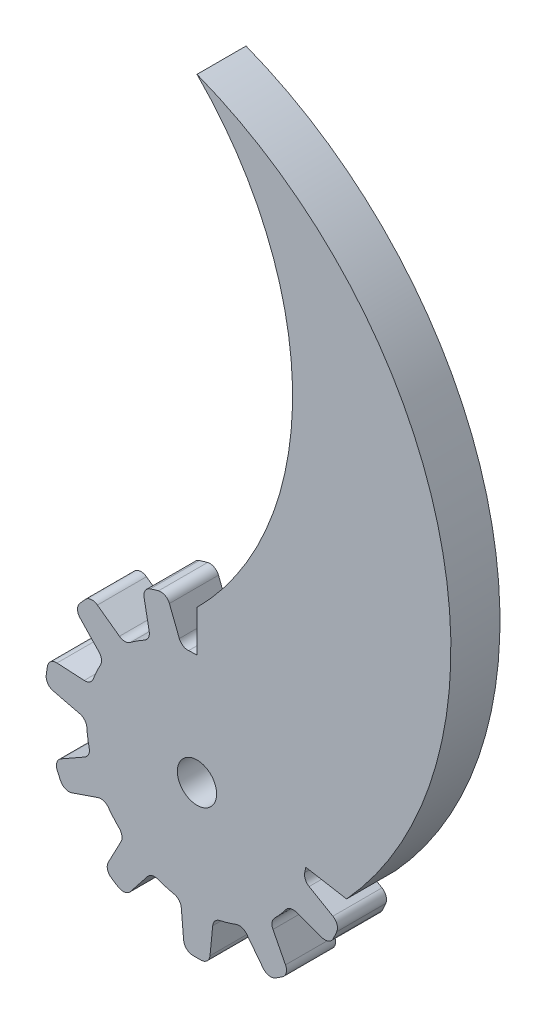
SolidWorks part; units mm, degrees
material "ABS"
ref_plane "Plano frontal" through (0, 0, 0) normal (0, 0, 1) x (1, 0, 0)
ref_plane "Plano superior" through (0, 0, 0) normal (0, 1, 0) x (1, 0, 0)
ref_plane "Plano direito" through (0, 0, 0) normal (1, 0, 0) x (0, 0, -1)
sketch "Esboço1" plane through (0, 0, 0) normal (0, 0, 1) x (1, 0, 0)
  line L0 (-5.4289, -10.4113) -> (-4.0402, -8.6536)
  line L1 (-7.2321, -9.242) -> (-6.1976, -7.2764)
  line L2 (-10.1959, -5.8234) -> (-8.0773, -5.0956)
  line L3 (-11.0806, -3.8649) -> (-9.1477, -2.7707)
  line L4 (-11.7257, 0.6133) -> (-9.5499, 0.0802)
  line L5 (-11.4112, 2.7393) -> (-9.1935, 2.6148)
  line L6 (-9.5327, 6.8553) -> (-7.9905, 5.2306)
  line L7 (-8.1187, 8.4738) -> (-6.3204, 7.1701)
  line L8 (-4.3131, 10.9208) -> (-3.8942, 8.7202)
  line L9 (-2.2487, 11.5179) -> (-1.4406, 9.4489)
  line L10 (1.0616, -11.6936) -> (1.2797, -9.4641)
  line L11 (-1.0874, -11.6849) -> (-1.2798, -9.472)
  line L12 (2.2758, 11.519) -> (1.4385, 9.4413)
  line L13 (4.3354, 10.9052) -> (3.8965, 8.7278)
  line L14 (8.1422, 8.46) -> (6.3145, 7.1648)
  line L15 (9.5429, 6.8302) -> (7.9966, 5.2356)
  line L16 (11.4235, 2.715) -> (9.1857, 2.6136)
  line L17 (11.7207, 0.5866) -> (9.5577, 0.0812)
  line L18 (11.0779, -3.892) -> (9.1405, -2.7675)
  line L19 (10.1772, -5.8432) -> (8.0844, -5.099)
  line L20 (7.2152, -9.2633) -> (6.1933, -7.2699)
  line L21 (5.4025, -10.4178) -> (4.0443, -8.6603)
  arc A0 (1.8703, -8.8035) -> (3.1854, -8.4174) centre (0, 0) ccw
  circle A1 centre (0, 0) radius 1.6
  arc A2 (-0.3622, -12.3696) -> (0.3355, -12.3703) centre (0, 0) ccw
  arc A3 (-1.0874, -11.6849) -> (-0.3622, -12.3696) centre (-0.3402, -11.6199) ccw
  arc A4 (1.0616, -11.6936) -> (0.3355, -12.3703) centre (0.3152, -11.6206) cw
  arc A5 (-6.9922, -10.2102) -> (-6.4056, -10.588) centre (0, 0) ccw
  arc A6 (-7.2321, -9.242) -> (-6.9922, -10.2102) centre (-6.5684, -9.5913) ccw
  arc A7 (-5.4289, -10.4113) -> (-6.4056, -10.588) centre (-6.0174, -9.9463) cw
  arc A8 (-11.4022, -4.8091) -> (-11.1131, -5.444) centre (0, 0) ccw
  arc A9 (-11.0806, -3.8649) -> (-11.4022, -4.8091) centre (-10.7112, -4.5176) ccw
  arc A10 (-10.1959, -5.8234) -> (-11.1131, -5.444) centre (-10.4395, -5.1141) cw
  arc A11 (-12.1921, 2.1188) -> (-12.2922, 1.4284) centre (0, 0) ccw
  arc A12 (-11.4112, 2.7393) -> (-12.1921, 2.1188) centre (-11.4532, 1.9904) ccw
  arc A13 (-11.7257, 0.6133) -> (-12.2922, 1.4284) centre (-11.5472, 1.3418) cw
  arc A14 (-9.1111, 8.3741) -> (-9.5686, 7.8473) centre (0, 0) ccw
  arc A15 (-8.1187, 8.4738) -> (-9.1111, 8.3741) centre (-8.5589, 7.8665) ccw
  arc A16 (-9.5327, 6.8553) -> (-9.5686, 7.8473) centre (-8.9887, 7.3717) cw
  arc A17 (-3.1374, 11.9706) -> (-3.8071, 11.7747) centre (0, 0) ccw
  arc A18 (-2.2487, 11.5179) -> (-3.1374, 11.9706) centre (-2.9473, 11.2451) ccw
  arc A19 (-4.3131, 10.9208) -> (-3.8071, 11.7747) centre (-3.5763, 11.0611) cw
  arc A20 (3.8324, 11.7665) -> (3.1632, 11.9638) centre (0, 0) ccw
  arc A21 (4.3354, 10.9052) -> (3.8324, 11.7665) centre (3.6001, 11.0534) ccw
  arc A22 (2.2758, 11.519) -> (3.1632, 11.9638) centre (2.9715, 11.2387) cw
  arc A23 (9.5855, 7.8266) -> (9.1291, 8.3544) centre (0, 0) ccw
  arc A24 (9.5429, 6.8302) -> (9.5855, 7.8266) centre (9.0045, 7.3523) ccw
  arc A25 (8.1422, 8.46) -> (9.1291, 8.3544) centre (8.5759, 7.8481) cw
  arc A26 (12.2952, 1.4019) -> (12.1967, 2.0926) centre (0, 0) ccw
  arc A27 (11.7207, 0.5866) -> (12.2952, 1.4019) centre (11.55, 1.3169) ccw
  arc A28 (11.4235, 2.715) -> (12.1967, 2.0926) centre (11.4575, 1.9658) cw
  arc A29 (11.1013, -5.4679) -> (11.3918, -4.8336) centre (0, 0) ccw
  arc A30 (10.1772, -5.8432) -> (11.1013, -5.4679) centre (10.4285, -5.1365) ccw
  arc A31 (11.0779, -3.892) -> (11.3918, -4.8336) centre (10.7014, -4.5407) cw
  arc A32 (6.3828, -10.6017) -> (6.9702, -10.2252) centre (0, 0) ccw
  arc A33 (5.4025, -10.4178) -> (6.3828, -10.6017) centre (5.996, -9.9592) ccw
  arc A34 (7.2152, -9.2633) -> (6.9702, -10.2252) centre (6.5477, -9.6055) cw
  arc A35 (6.3329, -6.3948) -> (7.2305, -5.359) centre (0, 0) ccw
  arc A36 (8.7849, -1.9559) -> (8.98, -0.5992) centre (0, 0) ccw
  arc A37 (8.4477, 3.1041) -> (7.8784, 4.3509) centre (0, 0) ccw
  arc A38 (5.4285, 7.1785) -> (4.2755, 7.9196) centre (0, 0) ccw
  arc A39 (0.6857, 8.9738) -> (-0.6849, 8.9739) centre (0, 0) ccw
  arc A40 (-4.2748, 7.92) -> (-5.4278, 7.179) centre (0, 0) ccw
  arc A41 (-7.878, 4.3516) -> (-8.4475, 3.1049) centre (0, 0) ccw
  arc A42 (-8.9801, -0.5984) -> (-8.7851, -1.9551) centre (0, 0) ccw
  arc A43 (-7.231, -5.3584) -> (-6.3335, -6.3943) centre (0, 0) ccw
  arc A44 (-3.1862, -8.4171) -> (-1.8711, -8.8034) centre (0, 0) ccw
  arc A45 (-6.3204, 7.1701) -> (-5.4278, 7.179) centre (-5.8802, 7.7773) ccw
  arc A46 (-3.8942, 8.7202) -> (-4.2748, 7.92) centre (-4.631, 8.58) cw
  arc A47 (-1.4406, 9.4489) -> (-0.6849, 8.9739) centre (-0.742, 9.7217) ccw
  arc A48 (1.4385, 9.4413) -> (0.6857, 8.9738) centre (0.7429, 9.7217) cw
  arc A49 (3.8965, 8.7278) -> (4.2755, 7.9196) centre (4.6318, 8.5796) ccw
  arc A50 (6.3145, 7.1648) -> (5.4285, 7.1785) centre (5.8809, 7.7768) cw
  arc A51 (7.9966, 5.2356) -> (7.8784, 4.3509) centre (8.535, 4.7135) ccw
  arc A52 (9.1857, 2.6136) -> (8.4477, 3.1041) centre (9.1517, 3.3628) cw
  arc A53 (9.5577, 0.0812) -> (8.98, -0.5992) centre (9.7284, -0.6491) ccw
  arc A54 (9.1405, -2.7675) -> (8.7849, -1.9559) centre (9.517, -2.1188) cw
  arc A55 (8.0844, -5.099) -> (7.2305, -5.359) centre (7.8331, -5.8056) ccw
  arc A56 (-7.9905, 5.2306) -> (-7.878, 4.3516) centre (-8.5345, 4.7143) cw
  arc A57 (-9.1935, 2.6148) -> (-8.4475, 3.1049) centre (-9.1514, 3.3636) ccw
  arc A58 (-9.5499, 0.0802) -> (-8.9801, -0.5984) centre (-9.7284, -0.6482) cw
  arc A59 (-9.1477, -2.7707) -> (-8.7851, -1.9551) centre (-9.5172, -2.118) ccw
  arc A60 (-8.0773, -5.0956) -> (-7.231, -5.3584) centre (-7.8336, -5.8049) cw
  arc A61 (-6.1976, -7.2764) -> (-6.3335, -6.3943) centre (-6.8613, -6.9271) ccw
  arc A62 (-4.0402, -8.6536) -> (-3.1862, -8.4171) centre (-3.4517, -9.1186) cw
  arc A63 (-1.8711, -8.8034) -> (-1.2798, -9.472) centre (-2.027, -9.537) cw
  arc A64 (1.8703, -8.8035) -> (1.2797, -9.4641) centre (2.0261, -9.5372) ccw
  arc A65 (4.0443, -8.6603) -> (3.1854, -8.4174) centre (3.4509, -9.1189) ccw
  arc A66 (6.1933, -7.2699) -> (6.3329, -6.3948) centre (6.8607, -6.9278) cw
  point P94 (0, 0)
  dimension "D1" = 3.2
  dimension "D2" = 11
extrude "Ressalto-extrusão1" add sketch "Esboço1" along normal blind 4
sketch "Esboço6" plane through (0, 0, 4) normal (0, 0, 1) x (1, 0, 0)
  line L0 (0, 50) -> (0, 0) construction
  line L1 (-18.815, 31.185) -> (0, 50) construction
  line L2 (-18.815, 31.185) -> (0, 12.37) construction
  line L3 (0, 9) -> (0, 12.37)
  line L4 (12.1921, -2.1188) -> (8.8671, -1.541)
  arc A1 (0, 12.37) -> (0, 50) centre (-18.815, 31.185) ccw
  arc A2 (12.1921, -2.1188) -> (0, 50) centre (-11.7234, 19.7721) ccw
  arc A4 (8.8671, -1.541) -> (0, 9) centre (0, 0) ccw
  dimension "D2" = 90
  dimension "D1" = 50
extrude "Ressalto-extrusão2" add sketch "Esboço6" against normal blind 4 contours A4 L4 A2 A1 L3 region at (11.6052, 20.8361, 4)
